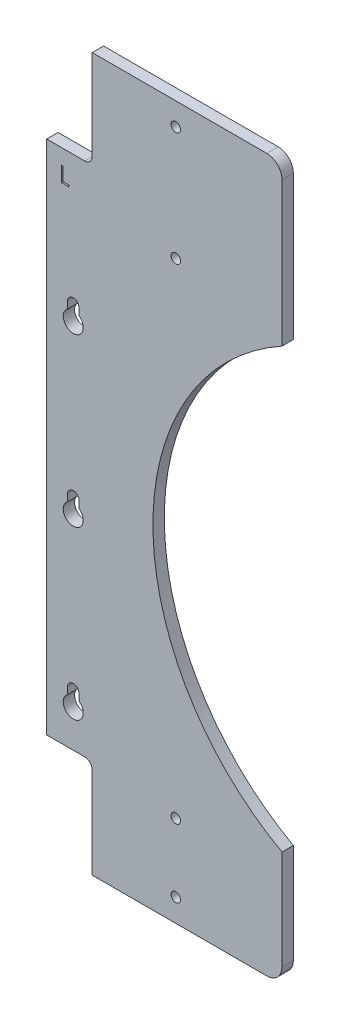
SolidWorks part; units mm, degrees
material "PC High Viscosity"
ref_plane "Front Plane" through (0, 0, 0) normal (0, 0, 1) x (1, 0, 0)
ref_plane "Top Plane" through (0, 0, 0) normal (0, 1, 0) x (1, 0, 0)
ref_plane "Right Plane" through (0, 0, 0) normal (1, 0, 0) x (0, 0, -1)
sketch "Sketch1" plane through (0, 0, 0) normal (0, 0, 1) x (1, 0, 0)
  line L0 (-174.625, 151.522) -> (-174.625, 311.15)
  line L1 (-174.625, -311.15) -> (174.625, -311.15)
  line L2 (-174.625, -311.15) -> (-174.625, -215.022)
  line L3 (-174.625, 311.15) -> (174.625, 311.15)
  line L4 (174.625, -311.15) -> (174.625, -215.022)
  line L5 (-174.625, -311.15) -> (174.625, 311.15) construction
  line L6 (-174.625, 311.15) -> (174.625, -311.15) construction
  line L7 (0, 311.15) -> (0, -311.15) construction
  line L8 (174.625, 151.522) -> (174.625, 311.15)
  line L10 (-316.9334, 298.842) -> (316.9334, 298.842) construction
  line L11 (-316.9334, 298.842) -> (-316.9334, 286.142) construction
  line L12 (-316.9334, 286.142) -> (316.9334, 286.142) construction
  line L13 (316.9334, 298.842) -> (316.9334, 286.142) construction
  arc A0 (-174.625, -215.022) -> (-174.625, 151.522) centre (-276.225, -31.75) ccw
  arc A1 (174.625, -215.022) -> (174.625, 151.522) centre (276.225, -31.75) cw
  point P0 (0, 0)
  point P14 (0, 249.0718)
  dimension "D3" = 419.1
  dimension "D1" = 622.3
  dimension "D2" = 349.25
  dimension "D4" = 279.4
  dimension "D5" = 101.6
  dimension "D6" = 12.7
  dimension "D7" = 134.62
extrude "Boss-Extrude1" add sketch "Sketch1" along normal blind 9.525
sketch "Sketch2" plane through (0, 0, 9.525) normal (0, 0, 1) x (1, 0, 0)
  line L0 (0, 311.15) -> (0, -311.15) construction
  line L1 (174.625, 311.15) -> (-174.625, 311.15) construction
  line L2 (-174.625, -311.15) -> (174.625, -311.15) construction
  line L3 (-66.675, -31.75) -> (66.675, -31.75) construction
  arc A0 (-174.625, -215.022) -> (-174.625, 151.522) centre (-276.225, -31.75) ccw construction
  arc A1 (174.625, 151.522) -> (174.625, -215.022) centre (276.225, -31.75) ccw construction
  point P6 (0, -191.262)
  point P7 (0, 88.138)
  point P16 (0, -51.562)
  dimension "D2" = 119.888
  dimension "D1" = 279.4
  dimension "D3" = 139.7
hole_wizard "V (0.377) Diameter Slot2" positions "Sketch3" profile "Sketch5" size "V" standard "ANSI Inch" slot yes end condition through all
sketch "Sketch3" plane through (0, 0, 9.525) normal (0, 0, 1) x (1, 0, 0)
  line L1 (0, -202.3745) -> (0, -180.1495) construction
  point P0 (0, -191.262)
  point P3 (0, 88.138)
  point P10 (0, -51.562)
  dimension "D1" = 22.225
sketch "Sketch5" plane through (0, -191.262, 9.525) normal (1, 0, 0) x (0, -1, 0)
  line L0 (0, 0) -> (0, 9.525)
  line L1 (0, 9.525) -> (4.7879, 9.525)
  line L2 (4.7879, 9.525) -> (4.7879, 0)
  line L5 (4.7879, 0) -> (0, 0)
  line L11 (0, -6.35) -> (0, 107.95) construction
  dimension "Thru Hole Dia." = 9.5758
  dimension "Thru Hole Depth" = 9.525
sketch "Sketch6" plane through (0, 0, 9.525) normal (0, 0, 1) x (1, 0, 0)
  line L0 (-174.625, -311.15) -> (174.625, -311.15) construction
  line L1 (-174.625, 311.15) -> (-22.225, 311.15)
  line L2 (-174.625, 311.15) -> (-174.625, -311.15)
  line L3 (-174.625, -311.15) -> (-22.225, -311.15)
  line L4 (-22.225, 311.15) -> (-22.225, -311.15)
  line L5 (174.625, 151.522) -> (174.625, 311.15) construction
  dimension "D1" = 196.85
extrude "Cut-Extrude1" cut sketch "Sketch6" against normal up to next
fillet "Fillet1" radius 12.7 1 edges at (174.625, -311.15, 4.7625)
sketch "Sketch7" plane through (0, 0, 9.525) normal (0, 0, 1) x (1, 0, 0)
  circle A0 centre (0, -197.5866) radius 8.382
  circle A1 centre (0, 81.8134) radius 8.382
  circle A2 centre (0, -57.8866) radius 8.382
  dimension "D1" = 16.764
extrude "Cut-Extrude2" cut sketch "Sketch7" against normal through all
sketch "Sketch9" plane through (0, 0, 9.525) normal (0, 0, 1) x (1, 0, 0)
  line L0 (137.2235, 251.5345) -> (137.2235, 184.8595) construction
  line L2 (174.625, 151.522) -> (174.625, 311.15) construction
  point P2 (137.2235, 218.197)
  dimension "D1" = 66.675
  dimension "D2" = 66.675
  dimension "D3" = 37.4015
sketch "Sketch12" plane through (0, 0, 9.525) normal (0, 0, 1) x (1, 0, 0)
  line L1 (-22.225, 311.15) -> (15.875, 311.15)
  line L2 (-22.225, 311.15) -> (-22.225, 203.2)
  line L3 (-22.225, 203.2) -> (15.875, 203.2)
  line L4 (15.875, 311.15) -> (15.875, 203.2)
  line L5 (-22.225, -311.15) -> (15.875, -311.15)
  line L6 (-22.225, -311.15) -> (-22.225, -228.6)
  line L7 (-22.225, -228.6) -> (15.875, -228.6)
  line L8 (15.875, -311.15) -> (15.875, -228.6)
  dimension "D1" = 38.1
  dimension "D2" = 107.95
  dimension "D3" = 82.55
extrude "Cut-Extrude3" cut sketch "Sketch12" against normal through all
fillet "Fillet2" radius 6.35 2 edges at (15.875, -228.6, 4.7625) (15.875, 203.2, 4.7625)
sketch "Sketch13" plane through (0, 0, 9.525) normal (0, 0, 1) x (1, 0, 0)
  line L0 (85.7885, 311.15) -> (85.7885, 55.6865) construction
  line L1 (174.625, 311.15) -> (15.875, 311.15) construction
  line L2 (174.625, 151.522) -> (174.625, 311.15) construction
  arc A0 (174.625, 151.522) -> (174.625, -215.022) centre (276.225, -31.75) ccw construction
  point P9 (85.7885, 265.938)
  point P10 (85.7885, 170.688)
  dimension "D1" = 88.8365
  dimension "D2" = 95.25
  dimension "D3" = 45.212
hole_wizard "5/16 (0.3125) Diameter Hole1" positions "Sketch14" profile "Sketch15" hole size "5/16" standard "ANSI Inch" end condition through all
sketch "Sketch14" plane through (0, 0, 9.525) normal (0, 0, 1) x (1, 0, 0)
  point P0 (85.7885, 170.688)
  point P5 (85.7885, 265.938)
sketch "Sketch15" plane through (85.7885, 170.688, 9.525) normal (1, 0, 0) x (0, -1, 0)
  line L0 (0, 0) -> (0, 9.525)
  line L1 (0, 9.525) -> (3.9687, 9.525)
  line L2 (3.9687, 9.525) -> (3.9687, 0)
  line L5 (3.9687, 0) -> (0, 0)
  line L11 (0, -6.35) -> (0, 107.95) construction
  dimension "Thru Hole Dia." = 7.9375
  dimension "Thru Hole Depth" = 9.525
sketch "Sketch16" plane through (0, 0, 9.525) normal (0, 0, 1) x (1, 0, 0)
  line L0 (174.625, 151.522) -> (174.625, 311.15) construction
  line L1 (15.875, 311.15) -> (174.625, 311.15)
  line L2 (15.875, 311.15) -> (15.875, 284.872)
  line L3 (15.875, 284.872) -> (174.625, 284.872)
  line L4 (174.625, 311.15) -> (174.625, 284.872)
  dimension "D1" = 133.35
extrude "Cut-Extrude4" cut sketch "Sketch16" against normal through all
sketch "Sketch17" plane through (0, 0, 9.525) normal (0, 0, 1) x (1, 0, 0)
  line L9 (174.625, 284.872) -> (15.875, 284.872)
  line L10 (15.875, 284.872) -> (15.875, 209.55)
  line L11 (9.525, 203.2) -> (-22.225, 203.2)
  line L12 (-22.225, 203.2) -> (-22.225, -228.6)
  line L13 (-22.225, -228.6) -> (9.525, -228.6)
  line L14 (15.875, -234.95) -> (15.875, -311.15)
  line L15 (15.875, -311.15) -> (161.925, -311.15)
  line L16 (174.625, -298.45) -> (174.625, -215.022)
  line L17 (174.625, 151.522) -> (174.625, 284.872)
  line L18 (174.625, 284.872) -> (15.875, 284.872)
  line L19 (15.875, 284.872) -> (15.875, 209.55)
  line L20 (9.525, 203.2) -> (-22.225, 203.2)
  line L21 (-22.225, 203.2) -> (-22.225, -228.6)
  line L22 (-22.225, -228.6) -> (9.525, -228.6)
  line L23 (15.875, -234.95) -> (15.875, -311.15)
  line L24 (15.875, -311.15) -> (161.925, -311.15)
  line L25 (174.625, -298.45) -> (174.625, -215.022)
  line L26 (174.625, 151.522) -> (174.625, 284.872)
  arc A4 (9.525, 203.2) -> (15.875, 209.55) centre (9.525, 209.55) ccw
  arc A5 (15.875, -234.95) -> (9.525, -228.6) centre (9.525, -234.95) ccw
  arc A6 (161.925, -311.15) -> (174.625, -298.45) centre (161.925, -298.45) ccw
  arc A7 (174.625, 151.522) -> (174.625, -215.022) centre (276.225, -31.75) ccw
  arc A8 (9.525, 203.2) -> (15.875, 209.55) centre (9.525, 209.55) ccw
  arc A9 (15.875, -234.95) -> (9.525, -228.6) centre (9.525, -234.95) ccw
  arc A10 (161.925, -311.15) -> (174.625, -298.45) centre (161.925, -298.45) ccw
  arc A11 (174.625, 151.522) -> (174.625, -215.022) centre (276.225, -31.75) ccw
  dimension "D1" = 0
sketch "Sketch18" plane through (0, 0, 9.525) normal (0, 0, 1) x (1, 0, 0)
  line L0 (174.625, -292.1) -> (15.875, -292.1) construction
  line L1 (174.625, -298.45) -> (174.625, -215.022) construction
  line L2 (15.875, -234.95) -> (15.875, -311.15) construction
  line L3 (15.875, -234.95) -> (174.625, -234.95) construction
  line L5 (85.7885, -292.1) -> (85.7885, -234.95) construction
  line L6 (85.7885, 311.15) -> (85.7885, 55.6865) construction
  line L7 (15.875, -311.15) -> (161.925, -311.15) construction
  point P8 (85.7885, -234.95)
  point P9 (85.7885, -292.1)
  dimension "D1" = 57.15
  dimension "D2" = 19.05
hole_wizard "5/16 (0.3125) Diameter Hole2" positions "Sketch19" profile "Sketch20" hole size "5/16" standard "ANSI Inch" end condition through all
sketch "Sketch19" plane through (0, 0, 9.525) normal (0, 0, 1) x (1, 0, 0)
  point P0 (85.7885, -234.95)
  point P3 (85.7885, -292.1)
sketch "Sketch20" plane through (85.7885, -234.95, 9.525) normal (1, 0, 0) x (0, -1, 0)
  line L0 (0, 0) -> (0, 9.525)
  line L1 (0, 9.525) -> (3.9687, 9.525)
  line L2 (3.9687, 9.525) -> (3.9687, 0)
  line L5 (3.9687, 0) -> (0, 0)
  line L11 (0, -6.35) -> (0, 107.95) construction
  dimension "Thru Hole Dia." = 7.9375
  dimension "Thru Hole Depth" = 9.525
sketch "Sketch21" plane through (0, 0, 9.525) normal (0, 0, 1) x (1, 0, 0)
  line L0 (-22.225, -228.6) -> (9.525, -228.6) construction
  line L1 (0, -183.6039) -> (0, 95.7961) construction
  line L2 (-22.225, 203.2) -> (-22.225, -228.6) construction
  circle A0 centre (0, 95.7961) radius 3.2639
  circle A1 centre (0, -183.6039) radius 3.2639
  circle A2 centre (0, -184.9374) radius 4.7879
  dimension "D3" = 6.5278
  dimension "D1" = 279.4
  dimension "D2" = 44.9961
  dimension "D4" = 22.225
fillet "Fillet3" radius 12.7 1 edges at (174.625, 284.872, 4.7625)
sketch "Sketch22" plane through (0, 0, 9.525) normal (0, 0, -1) x (-1, 0, 0)
  line L0 (3.175, 177.8) -> (28.575, 177.8) construction
  line L3 (22.225, -228.6) -> (22.225, 203.2) construction
  line L4 (22.225, 203.2) -> (-9.525, 203.2) construction
  text T0 "L" font "Century Gothic" height 12.7
  dimension "D1" = 25.4
  dimension "D2" = 19.05
  dimension "D3" = 25.4
extrude "Cut-Extrude5" cut sketch "Sketch22" along normal blind 1.27
equation "\"D3@Sketch9\"=1.3875+.17/2"
equation "\"D3@Sketch2\"=\"D1@Sketch2\"/2"
